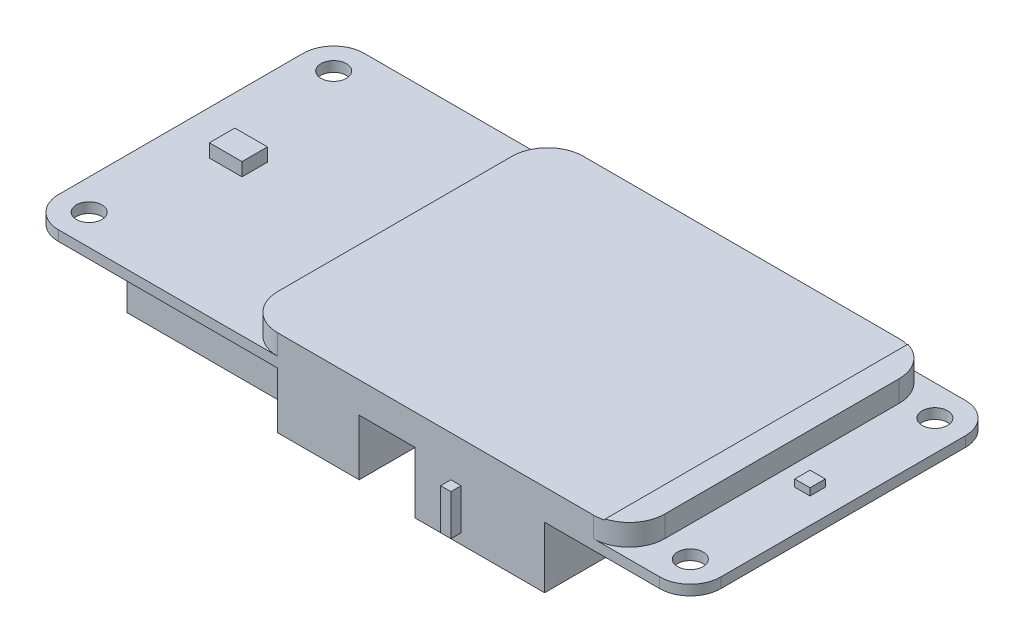
SolidWorks part; units mm, degrees
ref_plane "前视基准面" through (0, 0, 0) normal (0, 0, 1) x (1, 0, 0)
ref_plane "上视基准面" through (0, 0, 0) normal (0, 1, 0) x (1, 0, 0)
ref_plane "右视基准面" through (0, 0, 0) normal (1, 0, 0) x (0, 0, -1)
other "Configuration Table"
sketch "草图1" plane through (0, 0, 0) normal (0, 1, 0) x (1, 0, 0)
  line L1 (-29.5, 15) -> (29.5, 15)
  line L2 (-32.5, 12) -> (-32.5, -12)
  line L3 (-29.5, -15) -> (29.5, -15)
  line L4 (32.5, 12) -> (32.5, -12)
  line L5 (-32.5, 15) -> (32.5, -15) construction
  line L6 (-32.5, -15) -> (32.5, 15) construction
  arc A0 (29.5, -15) -> (32.5, -12) centre (29.5, -12) ccw
  arc A1 (29.5, 15) -> (32.5, 12) centre (29.5, 12) cw
  arc A2 (-32.5, -12) -> (-29.5, -15) centre (-29.5, -12) ccw
  arc A3 (-29.5, 15) -> (-32.5, 12) centre (-29.5, 12) ccw
  circle A4 centre (-29.5, 12) radius 1.25
  circle A5 centre (29.5, 12) radius 1.25
  circle A6 centre (-29.5, -12) radius 1.25
  circle A7 centre (29.5, -12) radius 1.25
  point P0 (0, 0)
  dimension "D3" = 3
  dimension "D4" = 2.5
  dimension "D1" = 65
  dimension "D2" = 30
extrude "board" add sketch "草图1" along normal blind 1
sketch "草图2" plane through (0, 1, 0) normal (0, 1, 0) x (1, 0, 0)
  line L0 (29.5, 15) -> (-29.5, 15) construction
  line L1 (-11.5, 15) -> (26.5, 15)
  line L2 (-11.5, 15) -> (-11.5, -15)
  line L3 (-11.5, -15) -> (26.5, -15)
  line L4 (26.5, 15) -> (26.5, -15)
  line L5 (-29.5, -15) -> (29.5, -15) construction
  line L6 (-32.5, 12) -> (-32.5, -12) construction
  line L7 (32.5, -12) -> (32.5, 12) construction
  dimension "D1" = 6
  dimension "D2" = 21
extrude "screen" add sketch "草图2" along normal blind 2
fillet "screen-radius" radius 3.5 4 edges at (-11.5, 2, -15) (26.5, 2, -15) (26.5, 2, 15) (-11.5, 2, 15)
sketch "草图9" plane through (0, 3, 0) normal (0, 1, 0) x (1, 0, 0)
  line L0 (26.5, -11.5) -> (26.5, 11.5) construction
  line L1 (26.5, -11.5) -> (26.5, 11.5)
  line L2 (24, 14.8541) -> (24, -14.8541)
  line L3 (32.5, -12) -> (32.5, 12) construction
  arc A0 (23, -15) -> (26.5, -11.5) centre (23, -11.5) ccw construction
  arc A1 (26.5, 11.5) -> (23, 15) centre (23, 11.5) ccw construction
  arc A2 (26.5, -11.5) -> (24, -14.8541) centre (23, -11.5) cw
  arc A3 (26.5, 11.5) -> (24, 14.8541) centre (23, 11.5) ccw
  dimension "D1" = 8.5
extrude "screen-top" add sketch "草图9" along normal blind 0.1
sketch "草图3" plane through (0, 0, 0) normal (0, -1, 0) x (1, 0, 0)
  line L0 (32.5, 12) -> (32.5, -12) construction
  line L1 (-25.5, -9) -> (25.5, -9)
  line L2 (-25.5, -9) -> (-25.5, -14)
  line L3 (-25.5, -14) -> (25.5, -14)
  line L4 (25.5, -9) -> (25.5, -14)
  line L6 (29.5, -15) -> (-29.5, -15) construction
  dimension "D1" = 5
  dimension "D2" = 51
  dimension "D3" = 7
  dimension "D4" = 1
extrude "plug" add sketch "草图3" along normal blind 5.2
sketch "草图4" plane through (0, 0, 0) normal (0, -1, 0) x (1, 0, 0)
  line L1 (-25.09, 12.68) -> (-9.95, 12.68)
  line L2 (-25.09, 12.68) -> (-25.09, -7.32)
  line L3 (-25.09, -7.32) -> (-9.95, -7.32)
  line L4 (-9.95, 12.68) -> (-9.95, -7.32)
  line L5 (-32.5, -12) -> (-32.5, 12) construction
  line L6 (-29.5, 15) -> (29.5, 15) construction
  dimension "D1" = 15.14
  dimension "D2" = 20
  dimension "D3" = 7.41
  dimension "D4" = 2.32
extrude "speaker" add sketch "草图4" along normal blind 5
sketch "草图10" plane through (0, 0, 0) normal (0, -1, 0) x (1, 0, 0)
  line L0 (-29.5, 15) -> (29.5, 15) construction
  line L1 (-8, 15) -> (0, 15)
  line L2 (-8, 15) -> (-8, 9)
  line L3 (-8, 9) -> (0, 9)
  line L4 (0, 15) -> (0, 9)
  line L5 (-32.5, -12) -> (-32.5, 12) construction
  dimension "D1" = 8
  dimension "D2" = 6
  dimension "D3" = 24.5
extrude "speaker2plug" add sketch "草图10" along normal blind 5.5
sketch "草图5" plane through (0, 0, 0) normal (0, -1, 0) x (1, 0, 0)
  line L1 (5.5, 15) -> (18.2, 15)
  line L2 (5.5, 15) -> (5.5, 9)
  line L3 (5.5, 9) -> (18.2, 9)
  line L4 (18.2, 15) -> (18.2, 9)
  line L5 (-29.5, 15) -> (-8, 15) construction
  line L6 (32.5, 12) -> (32.5, -12) construction
  dimension "D1" = 12.7
  dimension "D2" = 6
  dimension "D4" = 14.3
extrude "button" add sketch "草图5" along normal blind 6
sketch "草图6" plane through (0, 0, 15) normal (0, 0, 1) x (1, 0, 0)
  line L1 (18.2, -6) -> (5.5, -6) construction
  line L3 (9, -1) -> (10, -1)
  line L4 (9, -1) -> (9, -5)
  line L5 (9, -5) -> (10, -5)
  line L6 (10, -1) -> (10, -5)
  line L7 (-29.5, 0) -> (-8, 0) construction
  dimension "D2" = 1
  dimension "D3" = 1
  dimension "D4" = 1
extrude "button-tap" add sketch "草图6" along normal blind 1
sketch "草图7" plane through (0, 1, 0) normal (0, 1, 0) x (1, 0, 0)
  line L1 (28.5, 0.75) -> (30, 0.75)
  line L2 (28.5, 0.75) -> (28.5, -0.75)
  line L3 (28.5, -0.75) -> (30, -0.75)
  line L4 (30, 0.75) -> (30, -0.75)
  line L6 (32.5, -12) -> (32.5, 12) construction
  point P4 (32.5, 0)
  point P5 (30, 0)
  dimension "D1" = 1.5
  dimension "D2" = 1.5
  dimension "D4" = 2.5
extrude "rgb-led" add sketch "草图7" along normal blind 0.7
sketch "草图8" plane through (0, 1, 0) normal (0, 1, 0) x (1, 0, 0)
  line L0 (29.5, 15) -> (23, 15) construction
  line L1 (-25, 1) -> (-28.2, 1)
  line L2 (-25, 1) -> (-25, -1.5)
  line L3 (-25, -1.5) -> (-28.2, -1.5)
  line L4 (-28.2, 1) -> (-28.2, -1.5)
  line L6 (-32.5, 12) -> (-32.5, -12) construction
  dimension "D1" = 3.2
  dimension "D2" = 2.5
  dimension "D3" = 14
  dimension "D4" = 4.3
extrude "mic" add sketch "草图8" along normal blind 1.3
